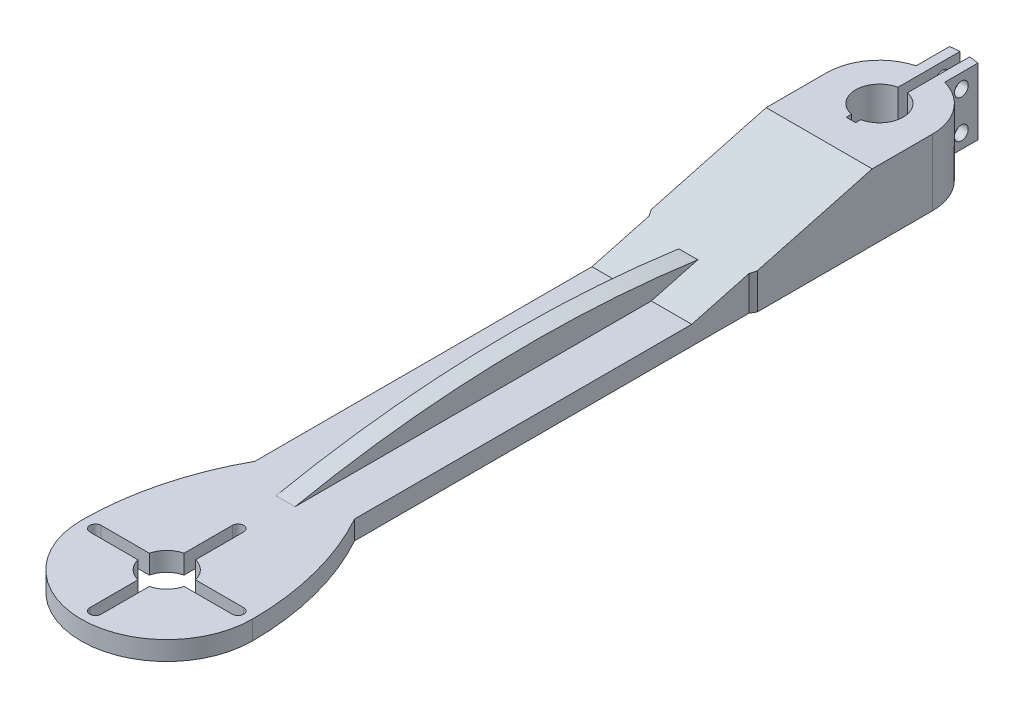
SolidWorks part; units mm, degrees
ref_plane "정면" through (0, 0, 0) normal (0, 0, 1) x (1, 0, 0)
ref_plane "윗면" through (0, 0, 0) normal (0, 1, 0) x (1, 0, 0)
ref_plane "우측면" through (0, 0, 0) normal (1, 0, 0) x (0, 0, -1)
sketch "스케치1" plane through (0, 0, 0) normal (0, 1, 0) x (1, 0, 0)
  line L0 (0, 0) -> (0, 150) construction
  line L1 (-15, 0) -> (15, 0) construction
  line L14 (-15, 1.2) -> (15, 1.2)
  line L15 (-15, -1.2) -> (15, -1.2)
  line L16 (0, 15) -> (0, -15) construction
  line L17 (1.2, 15) -> (1.2, -15)
  line L18 (-1.2, 15) -> (-1.2, -15)
  line L20 (-18, 150) -> (-18, 0)
  line L21 (18, 0) -> (18, 150)
  circle A0 centre (0, 150) radius 5
  arc A1 (-18, 150) -> (18, 150) centre (0, 150) cw
  circle A4 centre (0, 0) radius 5
  arc A5 (-15, 1.2) -> (-15, -1.2) centre (-15, 0) ccw
  arc A6 (15, -1.2) -> (15, 1.2) centre (15, 0) ccw
  arc A7 (1.2, 15) -> (-1.2, 15) centre (0, 15) ccw
  arc A8 (-1.2, -15) -> (1.2, -15) centre (0, -15) ccw
  arc A9 (-18, 0) -> (18, 0) centre (0, 0) ccw
  point P20 (0, 0)
  point P26 (0, 0)
  dimension "D2" = 10
  dimension "D8" = 10
  dimension "D11" = 1.2
  dimension "D12" = 1.2
  dimension "D13" = 18
  dimension "D1" = 150
  dimension "D9" = 30
  dimension "D10" = 30
extrude "보스-돌출1" add sketch "스케치1" along normal blind 4 contours L20 A9 L21 A1 A8 L18 A4 L15 A5 L14 A7 L17 A6 region at (0, 0, -76.2856)
sketch "스케치2" plane through (0, 4, 0) normal (0, 1, 0) x (1, 0, 0)
  line L0 (-18, 100) -> (18, 100)
  line L1 (-18, 150) -> (-18, 0) construction
  line L2 (18, 0) -> (18, 150) construction
  line L3 (18, 100) -> (18, 150)
  line L4 (-18, 150) -> (-18, 100)
  arc A0 (18, 150) -> (-18, 150) centre (0, 150) ccw
  circle A1 centre (0, 150) radius 5
  circle A3 centre (0, 150) radius 5 construction
  dimension "D1" = 50
extrude "보스-돌출2" add sketch "스케치2" along normal blind 10
sketch "스케치3" plane through (0, 0, 0) normal (1, 0, 0) x (0, 0, -1)
  line L0 (150, 14) -> (150, 0) construction
  circle A0 centre (150, 7) radius 1.45
  dimension "D1" = 2.9
sketch "스케치4" plane through (0, 4, 0) normal (0, 1, 0) x (1, 0, 0)
  line L0 (0, 0) -> (0, 150) construction
  line L1 (-10.5, 29.0474) -> (-10.5, 112.0096)
  line L2 (-10.5, 112.0096) -> (-18, 125)
  line L3 (-18, 150) -> (-18, 100) construction
  line L4 (-18, 125) -> (-18, 0)
  arc A0 (-18, 0) -> (-10.5, 29.0474) centre (42, 0) cw
  dimension "D1" = 60
  dimension "D2" = 21
  dimension "D3" = 30
  dimension "D4" = 125
extrude "컷-돌출2" cut sketch "스케치4" against normal through all both and the other way through all
mirror "대칭 복사1" about plane through (0, 0, 0) normal (1, 0, 0) of "컷-돌출2"
chamfer "모따기1" distance 10 angle 75 1 edges at (0, 14, -100) first distance on face at (0, 9, -100)
sketch "스케치5" plane through (0, 0, 0) normal (1, 0, 0) x (0, 0, -1)
  line L2 (25, 4) -> (125, 4)
  line L3 (29.0474, 4) -> (0, 4) construction
  arc A1 (25, 4) -> (125, 4) centre (75, -240.949) cw
  dimension "D1" = 25
  dimension "D3" = 250
  dimension "D2" = 100
extrude "보스-돌출3" add sketch "스케치5" along normal mid plane 4
sketch "스케치6" plane through (0, 14, 0) normal (0, 1, 0) x (1, 0, 0)
  line L0 (0, 0) -> (0, 168) construction
  line L1 (-3, 167.7482) -> (-3, 160.7482)
  line L2 (-11.1591, 150) -> (-11.1591, 113.1511)
  line L3 (-10.5, 112.0096) -> (-18, 125) construction
  line L4 (-11.1591, 113.1511) -> (-22.1591, 113.1511)
  line L5 (-22.1591, 113.1511) -> (-22.1591, 167.7482)
  line L6 (-22.1591, 167.7482) -> (-3, 167.7482)
  line L7 (22.1591, 167.7482) -> (3, 167.7482)
  line L8 (22.1591, 113.1511) -> (22.1591, 167.7482)
  line L9 (11.1591, 113.1511) -> (22.1591, 113.1511)
  line L10 (11.1591, 150) -> (11.1591, 113.1511)
  line L11 (3, 167.7482) -> (3, 160.7482)
  line L13 (-1, 192) -> (1, 192)
  line L14 (-1, 192) -> (-1, 144)
  line L15 (-1, 144) -> (1, 144)
  line L16 (1, 192) -> (1, 144)
  line L17 (-1, 192) -> (1, 144) construction
  line L18 (-1, 144) -> (1, 192) construction
  arc A0 (18, 150) -> (-18, 150) centre (0, 150) ccw construction
  arc A1 (-3, 160.7482) -> (-11.1591, 150) centre (0, 150) ccw
  arc A2 (3, 160.7482) -> (11.1591, 150) centre (0, 150) cw
  point P26 (2, 142.1395)
  dimension "D1" = 6
  dimension "D2" = 7
  dimension "D3" = 11
  dimension "D4" = 2
  dimension "D5" = 6
extrude "컷-돌출4" cut sketch "스케치6" against normal through all
sketch "스케치7" plane through (3, 0, 0) normal (1, 0, 0) x (0, 0, -1)
  line L0 (167.7482, 14) -> (160.7482, 14) construction
  line L1 (167.7482, 0) -> (160.7482, 0) construction
  circle A0 centre (164.2482, 11) radius 1.45
  circle A1 centre (164.2482, 3) radius 1.45
  point P4 (0, 0)
  point P7 (0, 0)
  point P10 (164.2482, 0)
  point P11 (163.02, 3.0949)
  dimension "D1" = 8
  dimension "D2" = 2.9
  dimension "D3" = 3
extrude "컷-돌출5" cut sketch "스케치7" against normal through all
